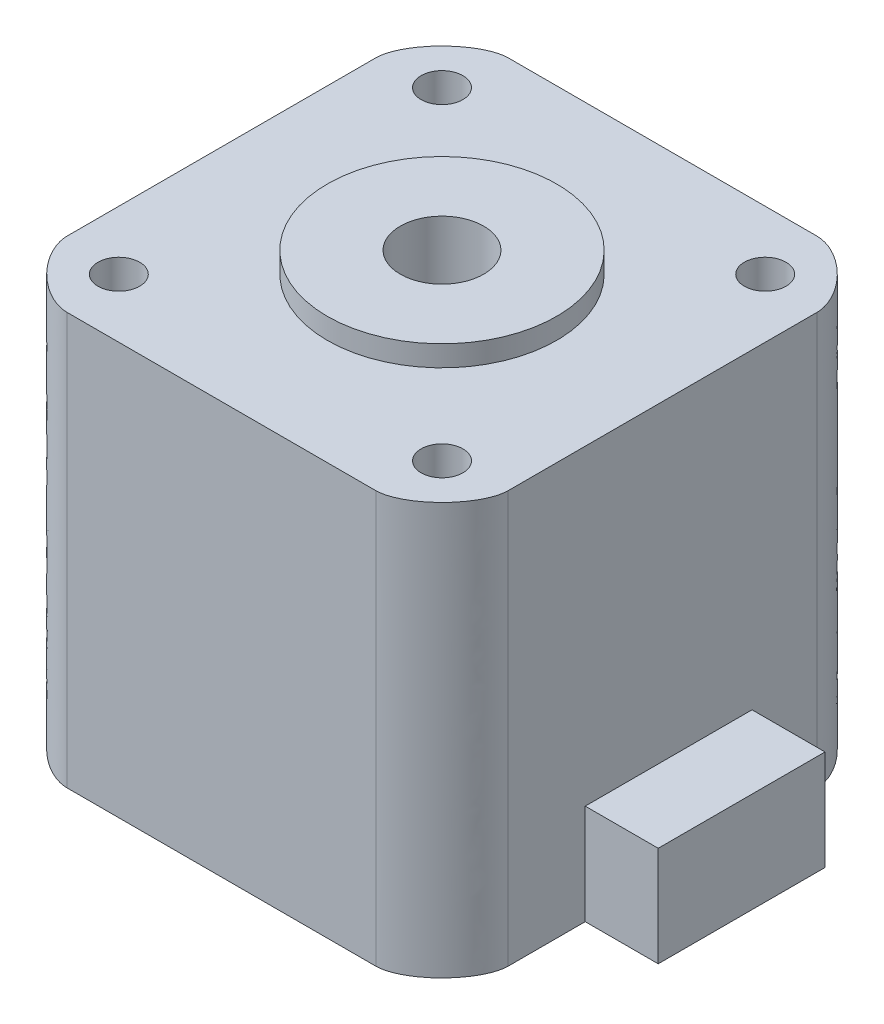
SolidWorks part; units mm, degrees
ref_plane "Front Plane" through (0, 0, 0) normal (0, 0, 1) x (1, 0, 0)
ref_plane "Top Plane" through (0, 0, 0) normal (0, 1, 0) x (1, 0, 0)
ref_plane "Right Plane" through (0, 0, 0) normal (1, 0, 0) x (0, 0, -1)
sketch "Sketch1" plane through (0, 0, 0) normal (0, 1, 0) x (1, 0, 0)
  line L1 (-14.7409, 17.4114) -> (27.5591, 17.4114)
  line L2 (-14.7409, 17.4114) -> (-14.7409, -24.8886)
  line L3 (-14.7409, -24.8886) -> (27.5591, -24.8886)
  line L4 (27.5591, 17.4114) -> (27.5591, -24.8886)
  dimension "D1" = 42.3
  dimension "D2" = 42.3
extrude "Boss-Extrude1" add sketch "Sketch1" along normal blind 39.5
sketch "Sketch2" plane through (0, 39.5, 0) normal (0, 1, 0) x (1, 0, 0)
  circle A0 centre (6.4091, -3.7386) radius 11
  dimension "D1" = 22
extrude "Boss-Extrude2" add sketch "Sketch2" along normal blind 2
fillet "Fillet1" radius 6.35 4 edges at (-14.7409, 19.75, -17.4114) (-14.7409, 19.75, 24.8886) (27.5591, 19.75, -17.4114) (27.5591, 19.75, 24.8886) conic radius 10
sketch "Sketch3" plane through (0, 39.5, 0) normal (0, 1, 0) x (1, 0, 0)
  line L0 (6.4091, -3.7386) -> (-35350.3007, 35350.2296) construction
  line L1 (6.4091, -3.7386) -> (35360.3773, 35352.9712) construction
hole_wizard "Ø4.0mm Dowel Hole1" positions "Sketch4" profile "Sketch5" hole size "Ø4.0" standard "ISO"
sketch "Sketch4" plane through (0, 39.5, 0) normal (0, 1, 0) x (1, 0, 0)
  line L0 (141433.2483, -141419.6117) -> (-176777.14, 176766.1026) construction
  line L1 (-141409.4639, -141430.5779) -> (176776.2504, 176779.8104) construction
  point P0 (-9.0921, 11.7614)
  point P4 (21.9079, 11.7614)
  point P8 (21.9103, -19.2386)
  point P10 (-9.0897, -19.2386)
  dimension "D1" = 31
  dimension "D2" = 31
  dimension "D3" = 31
  dimension "D4" = 31
sketch "Sketch5" plane through (-9.0921, 39.5, -11.7614) normal (1, 0, 0) x (0, 0, 1)
  line L0 (0, 0) -> (0, 5.7737)
  line L1 (0, 5.7737) -> (2, 4.572)
  line L2 (2, 4.572) -> (2, 0)
  line L5 (2, 0) -> (0, 0)
  line L10 (0, 5.7737) -> (-2, 4.572) construction
  line L11 (0, -6.35) -> (0, 107.95) construction
  dimension "Hole Dia." = 4
  dimension "Hole Depth" = 4.572
  dimension "Drill Angle" = 118
sketch "Sketch6" plane through (0, 41.5, 0) normal (0, 1, 0) x (1, 0, 0)
  circle A0 centre (6.4091, -3.7386) radius 4
  circle A1 centre (6.4091, -3.7386) radius 11 construction
  dimension "D1" = 8
extrude "Cut-Extrude1" cut sketch "Sketch6" against normal blind 37
sketch "Sketch7" plane through (27.5591, 0, 0) normal (1, 0, 0) x (0, 0, -1)
  line L0 (-18.5386, 0) -> (11.0614, 0) construction
  line L1 (-11.1511, 9.6) -> (4.8489, 9.6)
  line L2 (-11.1511, 9.6) -> (-11.1511, 0)
  line L3 (-11.1511, 0) -> (4.8489, 0)
  line L4 (4.8489, 9.6) -> (4.8489, 0)
  dimension "D1" = 16
  dimension "D2" = 9.6
extrude "Boss-Extrude3" add sketch "Sketch7" along normal blind 7
